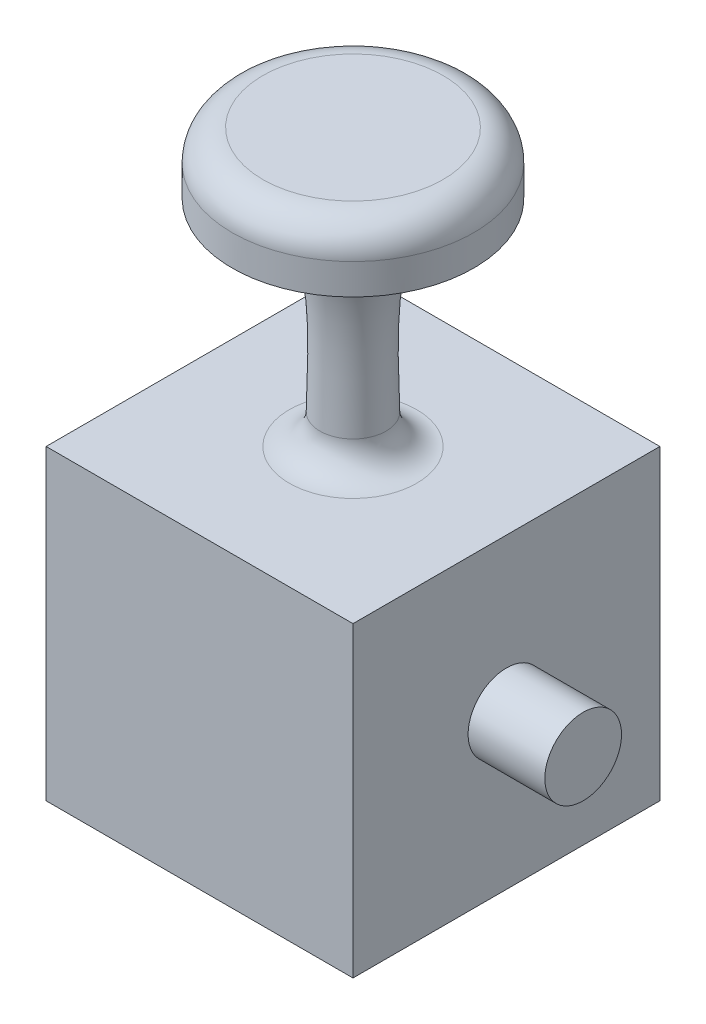
SolidWorks part; units mm, degrees
ref_plane "Front Plane" through (0, 0, 0) normal (0, 0, 1) x (1, 0, 0)
ref_plane "Top Plane" through (0, 0, 0) normal (0, 1, 0) x (1, 0, 0)
ref_plane "Right Plane" through (0, 0, 0) normal (1, 0, 0) x (0, 0, -1)
sketch "Sketch2" plane through (0, 0, 0) normal (1, 0, 0) x (0, 0, -1)
  line L1 (0, 0) -> (25.4, 0)
  line L2 (0, 0) -> (0, 25.4)
  line L3 (0, 25.4) -> (25.4, 25.4)
  line L4 (25.4, 0) -> (25.4, 25.4)
  dimension "D1" = 25.4
  dimension "D2" = 25.4
extrude "central box" add sketch "Sketch2" along normal blind 25.4
ref_point "center for extrusion of nibbles"
sketch "Sketch4" plane through (25.4, 0, 0) normal (1, 0, 0) x (0, 0, -1)
  circle A0 centre (12.7, 12.7) radius 3.175
  dimension "D1" = 6.35
extrude "nibbles" add sketch "Sketch4" along normal blind 6.35 and the other way blind 31.75
ref_point "stick extrusion spot"
ref_plane "stick drawin' plane" through (0, 0, -12.7) normal (0, 0, 1) x (1, 0, 0)
sketch "Sketch6" plane through (0, 0, -12.7) normal (0, 0, 1) x (1, 0, 0)
  line L0 (12.7, 25.4) -> (12.7, 48.26)
  line L1 (12.7, 48.26) -> (22.6999, 48.26)
  line L2 (22.6999, 48.26) -> (22.6999, 43.18)
  line L3 (12.7, 25.4) -> (15.494, 25.4)
  spline S0 degree 3 poles (22.6999, 43.18) (13.9762, 45.6623) (15.3846, 33.9482) (15.494, 25.4) knots 0 0 0 0 1 1 1 1
  dimension "D1" = 2.794
  dimension "D2" = 22.86
  dimension "D3" = 5.08
revolve "stick" add sketch "Sketch6" angle 360 about L0
fillet "yay, rounded" radius 2.54 2 edges at (12.7, 25.4, -15.494) (12.7, 48.26, -22.6999)
